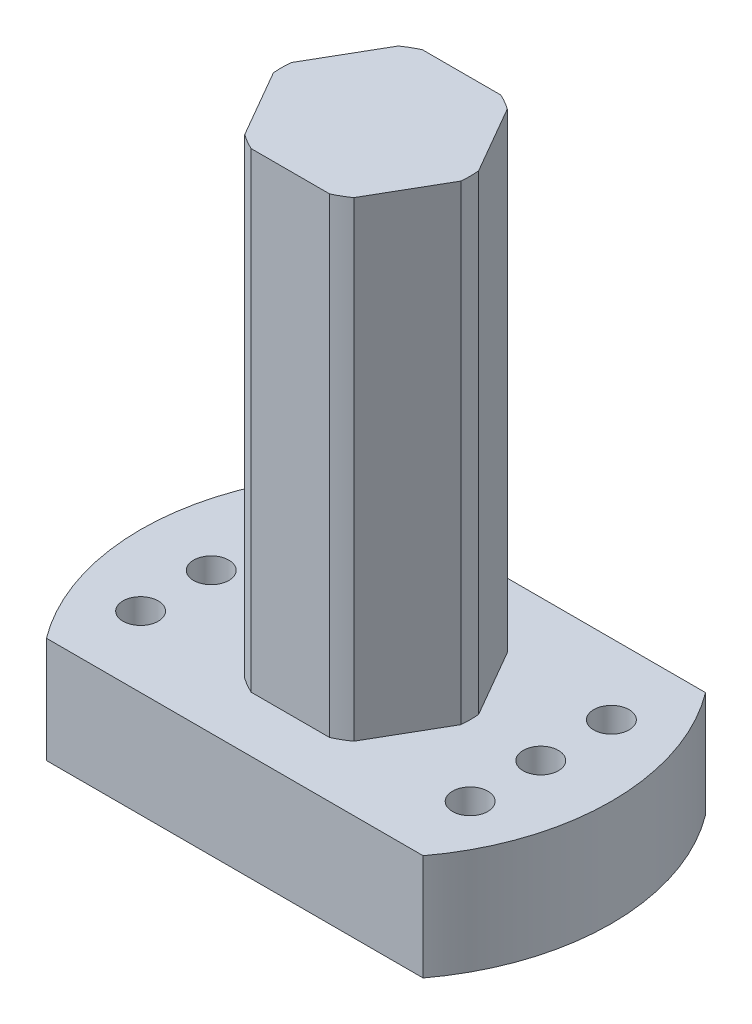
SolidWorks part; units mm, degrees
ref_plane "Спереди" through (0, 0, 0) normal (0, 0, 1) x (1, 0, 0)
ref_plane "Сверху" through (0, 0, 0) normal (0, 1, 0) x (1, 0, 0)
ref_plane "Справа" through (0, 0, 0) normal (1, 0, 0) x (0, 0, -1)
sketch "Эскиз1" plane through (0, 0, 0) normal (0, 1, 0) x (1, 0, 0)
  line L0 (0, -1000) -> (0, 49000) construction
  line L1 (-8, 6) -> (8, 6)
  line L3 (8, -6) -> (-8, -6)
  arc A0 (-8, 6) -> (-8, -6) centre (0, 0) ccw
  circle A12 centre (-7, 3) radius 0.75
  arc A14 (8, -6) -> (8, 6) centre (0, 0) ccw
  circle A15 centre (-7, 0) radius 0.75
  circle A16 centre (-7, -3) radius 0.75
  circle A17 centre (7, -3) radius 0.75
  circle A18 centre (7, 0) radius 0.75
  circle A19 centre (7, 3) radius 0.75
  point P29 (0, 0)
  dimension "D1" = 10
  dimension "D4" = 1.5
  dimension "D2" = 7
  dimension "D3" = 3
  dimension "D5" = 12
  dimension "D7" = 3
  dimension "D6" = 3
extrude "Бобышка-Вытянуть1" add sketch "Эскиз1" along normal blind 4.5
sketch "Эскиз2" plane through (0, 4.5, 0) normal (0, 1, 0) x (1, 0, 0)
  line L1 (1.6643, 3.6373) -> (-1.6643, 3.6373)
  line L2 (-2.3178, 3.26) -> (-3.9822, 0.3773)
  line L3 (-3.9822, -0.3773) -> (-2.3178, -3.26)
  line L4 (-1.6643, -3.6373) -> (1.6643, -3.6373)
  line L5 (2.3178, -3.26) -> (3.9822, -0.3773)
  line L6 (3.9822, 0.3773) -> (2.3178, 3.26)
  arc A1 (-1.6643, 3.6373) -> (-2.3178, 3.26) centre (0, 0) ccw
  arc A2 (2.3178, 3.26) -> (1.6643, 3.6373) centre (0, 0) ccw
  arc A3 (3.9822, -0.3773) -> (3.9822, 0.3773) centre (0, 0) ccw
  arc A4 (1.6643, -3.6373) -> (2.3178, -3.26) centre (0, 0) ccw
  arc A5 (-2.3178, -3.26) -> (-1.6643, -3.6373) centre (0, 0) ccw
  arc A6 (-3.9822, 0.3773) -> (-3.9822, -0.3773) centre (0, 0) ccw
  point P4 (0, 0)
  point P8 (0, 0)
  point P16 (0, 0)
  point P17 (0, 0)
  dimension "D1" = 8
  dimension "D2" = 3.3287
  dimension "D3" = 60
  dimension "D4" = 60
extrude "Бобышка-Вытянуть2" add sketch "Эскиз2" along normal blind 20
